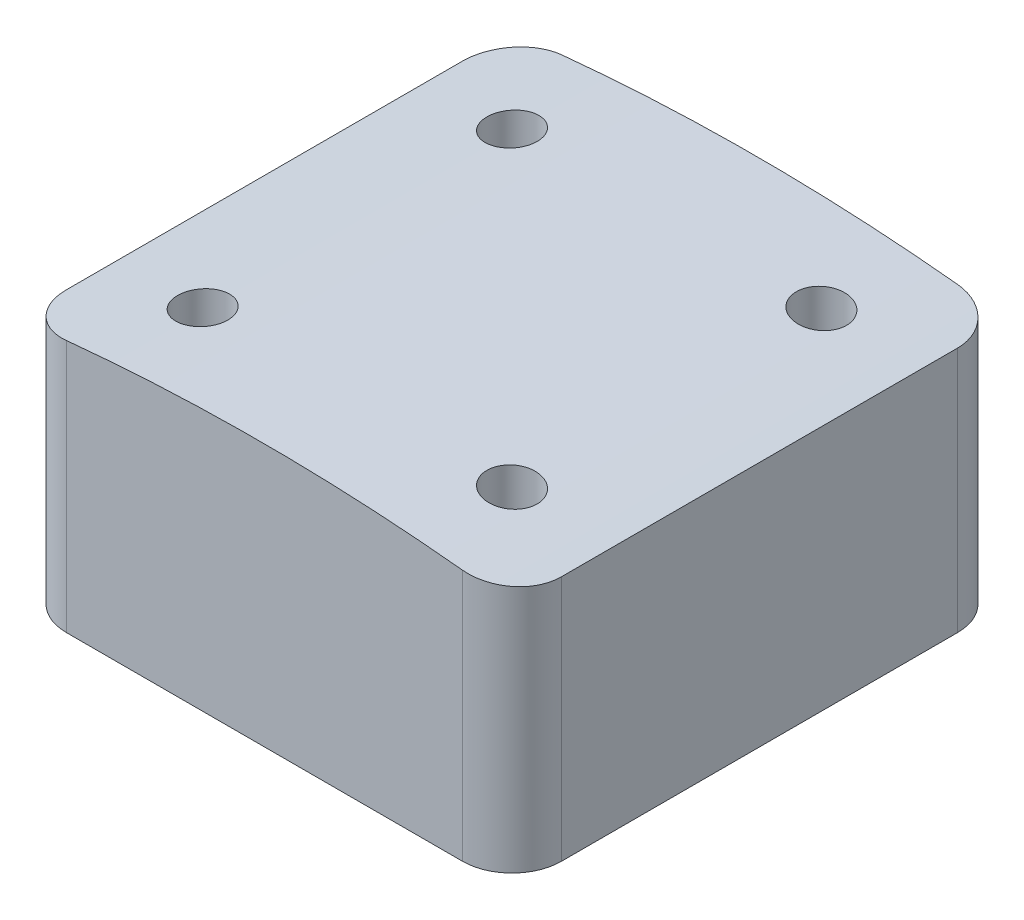
SolidWorks part; units mm, degrees
ref_plane "Front Plane" through (0, 0, 0) normal (0, 0, 1) x (1, 0, 0)
ref_plane "Top Plane" through (0, 0, 0) normal (0, 1, 0) x (1, 0, 0)
ref_plane "Right Plane" through (0, 0, 0) normal (1, 0, 0) x (0, 0, -1)
sketch "Sketch1" plane through (0, 0, 0) normal (0, 0, 1) x (1, 0, 0)
  line L0 (-12.7013, 100.8033) -> (-12.7013, 88.1033)
  line L6 (-12.7013, 88.1033) -> (12.6987, 88.1033)
  line L7 (12.6987, 88.1033) -> (12.6987, 100.7494)
  arc A0 (-12.7013, 100.8033) -> (12.6987, 100.7494) centre (-0.215, -0.0265) cw
extrude "Boss-Extrude1" add sketch "Sketch1" along normal blind 12.7 and the other way blind 12.7
sketch "Sketch2" plane through (0, 88.1033, 0) normal (0, -1, 0) x (1, 0, 0)
  circle A0 centre (0, 0) radius 4.7625
sketch "Sketch3" plane through (0, 88.1033, 0) normal (0, -1, 0) x (1, 0, 0)
  circle A0 centre (7.9375, -7.9375) radius 2.8448
  circle A1 centre (-7.9375, 7.9375) radius 3.0988
  circle A2 centre (7.9375, 7.9375) radius 2.8448
  circle A3 centre (-7.9375, -7.9375) radius 2.8448
hole_wizard "Tap Drill for 3/8-16 Tap1" positions "Sketch11" profile "Sketch10" hole size "3/8-16" standard "ANSI Inch"
sketch "Sketch11" plane through (0, 88.1033, 0) normal (0, -1, 0) x (-1, 0, 0)
  point P0 (0, 0)
sketch "Sketch10" plane through (0, 88.1033, 0) normal (1, 0, 0) x (0, 0, -1)
  line L0 (0, 0) -> (0, 11.9097)
  line L1 (0, 11.9097) -> (3.9687, 9.525)
  line L2 (3.9687, 9.525) -> (3.9687, 0)
  line L5 (3.9687, 0) -> (0, 0)
  line L10 (0, 11.9097) -> (-3.9688, 9.525) construction
  line L11 (0, -6.35) -> (0, 107.95) construction
  dimension "Hole Dia." = 7.9375
  dimension "Hole Depth" = 9.525
  dimension "Drill Angle" = 118
hole_wizard "#5-40 Tapped Hole1" positions "Sketch13" profile "Sketch12" tap size "#5-40" standard "ANSI Inch" end condition through all
sketch "Sketch13" plane through (0, 88.1033, 0) normal (0, -1, 0) x (-1, 0, 0)
  point P0 (-7.9375, -7.9375)
  point P3 (-7.9375, 7.9375)
  point P6 (7.9375, 7.9375)
  point P9 (7.9375, -7.9375)
sketch "Sketch12" plane through (7.9375, 88.1033, 7.9375) normal (1, 0, 0) x (0, 0, -1)
  line L0 (0, 0) -> (0, 13.4702)
  line L1 (0, 13.4702) -> (1.289, 13.4702)
  line L2 (1.289, 13.4702) -> (1.289, 0)
  line L5 (1.289, 0) -> (0, 0)
  line L11 (0, -6.35) -> (0, 107.95) construction
  dimension "Thread Major Dia." = 2.5781
  dimension "Thru Tap Drill Depth" = 13.4702
fillet "Fillet1" radius 2.54 4 edges at (12.6987, 94.4264, 12.7) (-12.7013, 94.4533, 12.7) (-12.7013, 94.4533, -12.7) (12.6987, 94.4264, -12.7)
